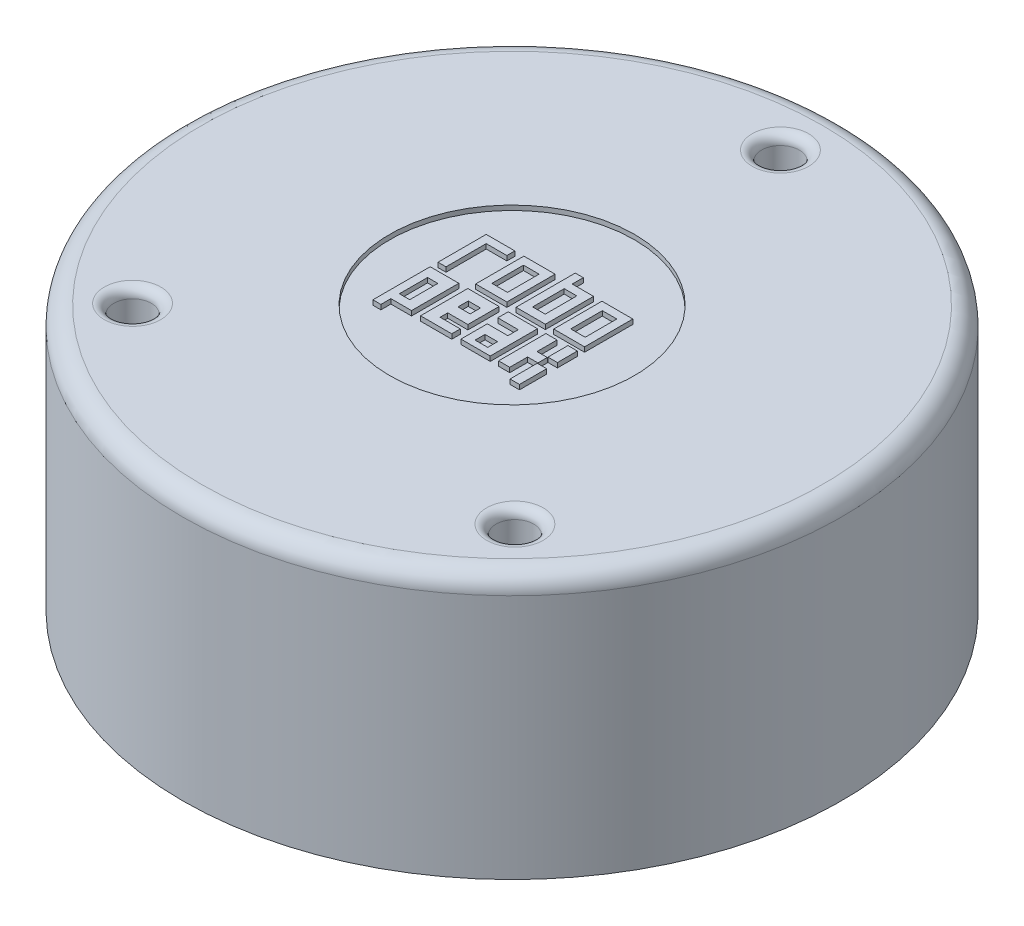
SolidWorks part; units mm, degrees
ref_plane "Спереди" through (0, 0, 0) normal (0, 0, 1) x (1, 0, 0)
ref_plane "Сверху" through (0, 0, 0) normal (0, 1, 0) x (1, 0, 0)
ref_plane "Справа" through (0, 0, 0) normal (1, 0, 0) x (0, 0, -1)
sketch "Эскиз1" plane through (0, 0, 0) normal (0, 1, 0) x (1, 0, 0)
  line L1 (-49.25, 35) -> (49.25, 35)
  line L2 (-49.25, 35) -> (-49.25, -35)
  line L3 (-49.25, -35) -> (49.25, -35)
  line L4 (49.25, 35) -> (49.25, -35)
  line L5 (-49.25, 35) -> (49.25, -35) construction
  line L6 (-49.25, -35) -> (49.25, 35) construction
  point P0 (0, 0)
  dimension "D1" = 98.5
  dimension "D2" = 70
extrude "Бобышка-Вытянуть1" add sketch "Эскиз1" along normal blind 5
sketch "Эскиз2" plane through (0, 5, 0) normal (0, 1, 0) x (1, 0, 0)
  line L0 (-49.25, 35) -> (-49.25, -35) construction
  circle A0 centre (-14.25, 0) radius 35
  point P2 (-49.25, 0)
  point P3 (-49.25, 0)
extrude "Бобышка-Вытянуть2" add sketch "Эскиз2" along normal blind 28.1
sketch "Эскиз3" plane through (0, 33.1, 0) normal (0, 1, 0) x (1, 0, 0)
  line L0 (-14.25, 0) -> (-14.25, 50000) construction
  line L1 (-14.25, -20) -> (-26.2883, -20) construction
  line L2 (-49.25, -35) -> (-14.25, -35) construction
  circle A0 centre (-14.25, 28.5) radius 2
  circle A1 centre (-34.5539, -20) radius 2
  circle A2 centre (6.0539, -20) radius 2
  arc A3 (-49.25, 0) -> (-14.25, -35) centre (-14.25, 0) ccw construction
  circle A4 centre (-14.25, 0) radius 35 construction
  dimension "D2" = 4
  dimension "D1" = 6.5
  dimension "D3" = 15
  dimension "D4" = 28.5
  dimension "D5" = 28.5
extrude "Вырез-Вытянуть1" cut sketch "Эскиз3" against normal blind 5
fillet "Скругление1" radius 2 1 edges at (-14.25, 33.1, 35)
fillet "Скругление2" radius 1 3 edges at (6.0539, 33.1, 22) (-34.5539, 33.1, 22) (-14.25, 33.1, -26.5)
sketch "Эскиз4" plane through (0, 33.1, 0) normal (0, 1, 0) x (1, 0, 0)
  line L0 (-22.1152, -6.9149) -> (-22.1152, -0.8316)
  line L1 (-22.1152, -0.8316) -> (-19.0735, -0.8316)
  line L2 (-19.0735, -0.8316) -> (-19.0735, -5.8538)
  line L3 (-19.0735, -5.8538) -> (-21.2663, -5.8538)
  line L4 (-21.2663, -5.8538) -> (-21.2663, -6.9149)
  line L5 (-21.2663, -6.9149) -> (-22.1152, -6.9149)
  line L6 (-22.1152, 0) -> (-22.1152, 5.1201)
  line L7 (-22.1152, 5.1201) -> (-19.0735, 5.1201)
  line L8 (-19.0735, 5.1201) -> (-19.0735, 4.2707)
  line L9 (-19.0735, 4.2707) -> (-21.2663, 4.2707)
  line L10 (-21.2663, 4.2707) -> (-21.2663, 0)
  line L11 (-21.2663, 0) -> (-22.1152, 0)
  line L12 (-21.2663, -1.9579) -> (-20.1699, -1.9579)
  line L13 (-20.1699, -1.9579) -> (-20.1699, -4.9509)
  line L14 (-20.1699, -4.9509) -> (-21.2663, -4.9509)
  line L15 (-21.2663, -4.9509) -> (-21.2663, -1.9579)
  line L16 (-13.8296, 0) -> (-13.8296, 6.293)
  line L17 (-18.1168, 0) -> (-14.8003, 0)
  line L18 (-18.1168, 0) -> (-18.1168, 5.1201)
  line L19 (-18.1168, 5.1201) -> (-14.8003, 5.1201)
  line L20 (-14.8003, 0) -> (-14.8003, 5.1201)
  line L21 (-9.8255, 5.1201) -> (-6.5494, 5.1201)
  line L22 (-9.8255, 5.1201) -> (-9.8255, 0)
  line L23 (-9.8255, 0) -> (-6.5494, 0)
  line L24 (-6.5494, 5.1201) -> (-6.5494, 0)
  line L25 (-8.9357, 4.2707) -> (-7.3988, 4.2707)
  line L26 (-8.9357, 4.2707) -> (-8.9357, 0.9137)
  line L27 (-8.9357, 0.9137) -> (-7.3988, 0.9137)
  line L28 (-7.3988, 4.2707) -> (-7.3988, 0.9137)
  line L29 (-17.3079, 4.2707) -> (-15.6497, 4.2707)
  line L30 (-17.3079, 4.2707) -> (-17.3079, 0.9137)
  line L31 (-17.3079, 0.9137) -> (-15.6497, 0.9137)
  line L32 (-15.6497, 4.2707) -> (-15.6497, 0.9137)
  line L33 (-12.9802, 4.2707) -> (-11.6455, 4.2707)
  line L34 (-12.9802, 4.2707) -> (-12.9802, 0.9137)
  line L35 (-12.9802, 0.9137) -> (-11.6455, 0.9137)
  line L36 (-11.6455, 4.2707) -> (-11.6455, 0.9137)
  line L37 (-12.9802, -4.142) -> (-11.6455, -4.142)
  line L38 (-12.9802, -4.142) -> (-12.9802, -5.1936)
  line L39 (-12.9802, -5.1936) -> (-11.6455, -5.1936)
  line L40 (-11.6455, -4.142) -> (-11.6455, -5.1936)
  line L41 (-16.9439, -1.9579) -> (-15.6497, -1.9579)
  line L42 (-16.9439, -1.9579) -> (-16.9439, -3.0499)
  line L43 (-16.9439, -3.0499) -> (-15.6497, -3.0499)
  line L44 (-15.6497, -1.9579) -> (-15.6497, -3.0499)
  line L46 (-7.5508, -0.7643) -> (-6.5494, -0.7643)
  line L47 (-7.5508, -0.7643) -> (-7.5508, -2.8858)
  line L48 (-7.5508, -2.8858) -> (-6.5494, -2.8858)
  line L49 (-6.5494, -0.7643) -> (-6.5494, -2.8858)
  line L50 (-6.5494, -6.9149) -> (-7.5508, -6.9149)
  line L51 (-6.5494, -6.9149) -> (-6.5494, -4.0216)
  line L52 (-6.5494, -4.0216) -> (-7.5508, -4.0216)
  line L53 (-13.8296, 6.293) -> (-12.9802, 6.293)
  line L54 (-12.9802, 6.293) -> (-12.9802, 5.1201)
  line L55 (-12.9802, 5.1201) -> (-10.7153, 5.1201)
  line L56 (-10.7153, 5.1201) -> (-10.7153, 0)
  line L57 (-10.7153, 0) -> (-13.8296, 0)
  line L58 (-9.8255, -0.8316) -> (-8.6437, -0.8316)
  line L59 (-8.6437, -0.8316) -> (-8.6437, -2.9608)
  line L60 (-8.6437, -2.9608) -> (-7.5508, -2.9608)
  line L61 (-9.8255, -0.8316) -> (-9.8255, -5.8538)
  line L62 (-9.8255, -5.8538) -> (-8.6437, -5.8538)
  line L63 (-8.6437, -5.8538) -> (-8.6437, -3.9573)
  line L64 (-8.6437, -3.9573) -> (-7.5508, -3.9573)
  line L65 (-7.5508, -2.9608) -> (-7.5508, -3.9573)
  line L66 (-13.8296, -0.8316) -> (-10.7153, -0.8316)
  line L67 (-10.7153, -0.8316) -> (-10.7153, -5.8538)
  line L68 (-10.7153, -5.8538) -> (-13.8296, -5.8538)
  line L69 (-13.8296, -5.8538) -> (-13.8296, -3.0499)
  line L70 (-13.8296, -3.0499) -> (-11.6455, -3.0499)
  line L71 (-11.6455, -3.0499) -> (-11.6455, -1.9408)
  line L72 (-11.6455, -1.9408) -> (-13.8296, -1.9408)
  line L73 (-13.8296, -1.9408) -> (-13.8296, -0.8316)
  line L74 (-18.1168, -0.8316) -> (-14.8003, -0.8316)
  line L75 (-14.8003, -0.8316) -> (-14.8003, -4.142)
  line L76 (-14.8003, -4.142) -> (-16.9439, -4.142)
  line L77 (-16.9439, -4.142) -> (-16.9439, -4.9509)
  line L78 (-16.9439, -4.9509) -> (-14.8003, -4.9509)
  line L79 (-14.8003, -4.9509) -> (-14.8003, -5.8538)
  line L80 (-14.8003, -5.8538) -> (-18.1168, -5.8538)
  line L81 (-18.1168, -5.8538) -> (-18.1168, -0.8316)
  line L82 (-7.5508, -6.9149) -> (-7.5508, -4.0216)
  circle A0 centre (-14.25, 0) radius 13
  dimension "D1" = 26
extrude "Вырез-Вытянуть3" cut sketch "Эскиз4" against normal blind 0.5 contours A0 L50 L82 L52 L51 L72 L73 L66 L67 L68 L69 L70 L71 L56 L57 L16 L53 L54 L55 L10 L11 L6 L7 L8 L9 L4 L5 L0 L1 L2 L3 L20 L17 L18 L19 L21 L24 L23 L22 L46 L49 L48 L47 | L32 L29 L30 L31 | L36 L33 L34 L35 | L28 L25 L26 L27 | L44 L41 L42 L43 | L15 L14 L13 L12 | L37 L40 L39 L38 region at (-20.7181, 33.1, 3.4544) region at (-8.1672, 33.1, -2.5922) region at (-16.4788, 33.1, -2.5922) region at (-12.3129, 33.1, -2.5922) region at (-16.2968, 33.1, 2.5039) region at (-14.2871, 33.1, -0.0991)
sketch "Эскиз5" plane through (0, 5, 0) normal (0, 1, 0) x (1, 0, 0)
  line L0 (-42.25, 30.7255) -> (-42.25, -39.5827) construction
  line L1 (27.75, 26.9972) -> (27.75, -49973.0028) construction
  line L2 (-49.25, 0) -> (49950.75, 0) construction
  circle A0 centre (-14.25, 0) radius 33 construction
  circle A1 centre (-42.25, 28) radius 1.25
  circle A2 centre (27.75, 20) radius 1.25
  circle A3 centre (27.75, -20) radius 1.25
  circle A4 centre (-42.25, -28) radius 1.25
  point P4 (-14.25, 33)
  dimension "D1" = 28
  dimension "D3" = 2.5
  dimension "D2" = 42
  dimension "D4" = 28
  dimension "D5" = 20
extrude "Вырез-Вытянуть4" cut sketch "Эскиз5" against normal blind 5
sketch "Эскиз6" plane through (0, 5, 0) normal (0, 1, 0) x (1, 0, 0)
  line L0 (49.25, 0) -> (50049.25, 0) construction
  line L1 (49.25, -35) -> (49.25, 35) construction
  circle A0 centre (31.25, 0) radius 9
  arc A1 (-14.25, -35) -> (-14.25, 35) centre (-14.25, 0) ccw construction
  point P4 (49.25, 0)
  dimension "D1" = 18
  dimension "D2" = 45.5
extrude "Бобышка-Вытянуть3" add sketch "Эскиз6" along normal blind 7
sketch "Эскиз7" plane through (0, 12, 0) normal (0, 1, 0) x (1, 0, 0)
  circle A0 centre (31.25, 0) radius 9
  circle A1 centre (31.25, 0) radius 0.9935
extrude "Вырез-Вытянуть5" cut sketch "Эскиз7" against normal blind 1
sketch "Эскиз8" plane through (0, 11, 0) normal (0, 1, 0) x (1, 0, 0)
  circle A0 centre (31.25, 0) radius 3.0011
  circle A1 centre (31.25, 0) radius 5.5217
extrude "Вырез-Вытянуть6" cut sketch "Эскиз8" against normal blind 1
fillet "Скругление3" radius 0.4 1 edges at (31.25, 12, 0.9935)
sketch "Эскиз9" plane through (0, 5, 0) normal (0, 1, 0) x (1, 0, 0)
  circle A0 centre (31.25, 0) radius 16
  dimension "D1" = 32
extrude "Бобышка-Вытянуть4" add sketch "Эскиз9" against normal blind 27
sketch "Эскиз10" plane through (0, 0, 0) normal (0, -1, 0) x (1, 0, 0)
  line L0 (-49.25, 0) -> (49950.75, 0) construction
  line L1 (-40.8546, 25.4729) -> (-39.3638, 27.9449)
  line L2 (-39.3638, 27.9449) -> (-40.7592, 30.472)
  line L3 (-40.7592, 30.472) -> (-43.6454, 30.5271)
  line L4 (-43.6454, 30.5271) -> (-45.1362, 28.0551)
  line L5 (-45.1362, 28.0551) -> (-43.7408, 25.528)
  line L6 (-43.7408, 25.528) -> (-40.8546, 25.4729)
  line L7 (29.2571, 22.4621) -> (26.3713, 22.5363)
  line L8 (26.3713, 22.5363) -> (24.8642, 20.0742)
  line L9 (24.8642, 20.0742) -> (26.2429, 17.5379)
  line L10 (26.2429, 17.5379) -> (29.1287, 17.4637)
  line L11 (29.1287, 17.4637) -> (30.6358, 19.9258)
  line L12 (30.6358, 19.9258) -> (29.2571, 22.4621)
  line L13 (30.6358, -19.9258) -> (29.2571, -22.4621)
  line L14 (29.1287, -17.4637) -> (30.6358, -19.9258)
  line L15 (26.2429, -17.5379) -> (29.1287, -17.4637)
  line L16 (24.8642, -20.0742) -> (26.2429, -17.5379)
  line L17 (26.3713, -22.5363) -> (24.8642, -20.0742)
  line L18 (29.2571, -22.4621) -> (26.3713, -22.5363)
  line L19 (-43.7408, -25.528) -> (-40.8546, -25.4729)
  line L20 (-45.1362, -28.0551) -> (-43.7408, -25.528)
  line L21 (-43.6454, -30.5271) -> (-45.1362, -28.0551)
  line L22 (-40.7592, -30.472) -> (-43.6454, -30.5271)
  line L23 (-39.3638, -27.9449) -> (-40.7592, -30.472)
  line L24 (-40.8546, -25.4729) -> (-39.3638, -27.9449)
  circle A0 centre (-42.25, 28) radius 2.5 construction
  circle A1 centre (27.75, 20) radius 2.5 construction
  circle A2 centre (27.75, -20) radius 2.5 construction
  circle A3 centre (-42.25, -28) radius 2.5 construction
  point P17 (27.75, 20)
  dimension "D1" = 5
  dimension "D2" = 5
extrude "Бобышка-Вытянуть5" add sketch "Эскиз10" along normal blind 38
sketch "Эскиз11" plane through (0, 5, 0) normal (0, 1, 0) x (1, 0, 0)
  circle A0 centre (-14.25, 0) radius 26
  dimension "D1" = 52
extrude "Бобышка-Вытянуть6" add sketch "Эскиз11" against normal blind 8
fillet "Скругление4" radius 1 1 edges at (-14.25, -3, 26)
sketch "Эскиз12" plane through (0, 5, 0) normal (0, 1, 0) x (1, 0, 0)
  line L1 (49.25, -35) -> (49.25, 35) construction
  line L2 (-49.25, 0) -> (-50049.25, 0) construction
  line L4 (-54.0511, 37.7308) -> (52.2004, 37.7308)
  line L5 (-54.0511, 37.7308) -> (-54.0511, -37.8351)
  line L6 (-54.0511, -37.8351) -> (52.2004, -37.8351)
  line L7 (52.2004, 37.7308) -> (52.2004, -37.8351)
  arc A0 (-49.25, 0) -> (-45.5286, 27.9743) centre (86.6751, -3.8473) cw
  circle A1 centre (-14.25, 0) radius 35 construction
  arc A3 (49.25, 0) -> (42.909, 13.5993) centre (31.4018, -0.0442) ccw
  arc A4 (-49.25, 0) -> (-14.25, -35) centre (-14.25, 0) ccw construction
  arc A5 (-42.835, 30.8555) -> (42.909, 13.5993) centre (-15.6796, -55.8665) cw
  arc A6 (-45.5286, 27.9743) -> (-42.835, 30.8555) centre (-41.6397, 27.0383) cw
  arc A7 (-45.5286, -27.9743) -> (-42.835, -30.8555) centre (-41.6397, -27.0383) ccw
  arc A8 (-42.835, -30.8555) -> (42.909, -13.5993) centre (-15.6796, 55.8665) ccw
  arc A9 (49.25, 0) -> (42.909, -13.5993) centre (31.4018, 0.0442) cw
  arc A10 (-49.25, 0) -> (-45.5286, -27.9743) centre (86.6751, 3.8473) ccw
  dimension "D1" = 4
extrude "Вырез-Вытянуть7" cut sketch "Эскиз12" against normal blind 8
fillet "Скругление5" radius 100 1 edges at (-49.25, 2.5, 0)
sketch "Эскиз13" plane through (0, 0, 0) normal (0, -1, 0) x (1, 0, 0)
  line L0 (31.5536, 21.8603) -> (31.5536, 16.4)
  line L1 (31.5536, -16.4) -> (31.5536, -21.8603)
  arc A0 (-49.0982, 0) -> (-45.3768, 27.9743) centre (86.8269, -3.8473) cw
  arc A1 (31.5536, 16.4) -> (31.5536, -16.4) centre (31.5536, 0) ccw
  arc A2 (-42.6831, 30.8555) -> (31.5536, 21.8603) centre (-15.5278, -55.8665) cw
  arc A3 (-45.3768, 27.9743) -> (-42.6831, 30.8555) centre (-41.4878, 27.0383) cw
  arc A4 (-45.3768, -27.9743) -> (-42.6831, -30.8555) centre (-41.4878, -27.0383) ccw
  arc A5 (-42.6831, -30.8555) -> (31.5536, -21.8603) centre (-15.5278, 55.8665) ccw
  arc A7 (-49.0982, 0) -> (-45.3768, -27.9743) centre (86.8269, 3.8473) ccw
  arc A8 (-48.5248, 10.6929) -> (-48.5248, -10.6929) centre (50.9018, 0) ccw construction
  point P16 (-49.0982, 0)
  point P21 (-49.0982, 0)
  dimension "D1" = 4
  dimension "D2" = 32.8
extrude "Бобышка-Вытянуть7" add sketch "Эскиз13" along normal blind 1.6 from offset 8
sketch "Эскиз14" plane through (0, -9.6, 0) normal (0, -1, 0) x (1, 0, 0)
  line L1 (-24.0982, 30) -> (-4.0982, 30)
  line L2 (-24.0982, 30) -> (-24.0982, 25)
  line L3 (-24.0982, 25) -> (-4.0982, 25)
  line L4 (-4.0982, 30) -> (-4.0982, 25)
  circle A0 centre (-14.25, 0) radius 35 construction
  point P4 (-14.0982, 30)
  dimension "D1" = 5
  dimension "D2" = 20
  dimension "D3" = 35
  dimension "D4" = 30
extrude "Бобышка-Вытянуть8" add sketch "Эскиз14" along normal blind 6
chamfer "Фаска1" distance 1 angle 45 1 edges at (-24.0982, -12.6, 30)
sketch "Sketch2" plane through (0, 0, 0) normal (1, 0, 0) x (0, 0, -1)
  line L0 (-4.0339, 5) -> (-10.6929, 5) construction
  line L1 (57.9181, 5) -> (-53.6731, 5)
  line L2 (57.9181, 5) -> (57.9181, -38)
  line L3 (57.9181, -38) -> (-53.6731, -38)
  line L4 (-53.6731, 5) -> (-53.6731, -38)
  dimension "D1" = 111.5912
extrude "Cut-Extrude2" cut sketch "Sketch2" against normal through all both and the other way through all
sketch "Sketch3" plane through (0, 5, 0) normal (0, -1, 0) x (1, 0, 0)
  circle A1 centre (31.25, 0) radius 9
  circle A2 centre (31.25, 0) radius 9
  dimension "D1" = 0
extrude "Cut-Extrude3" cut sketch "Sketch3" against normal blind 10
